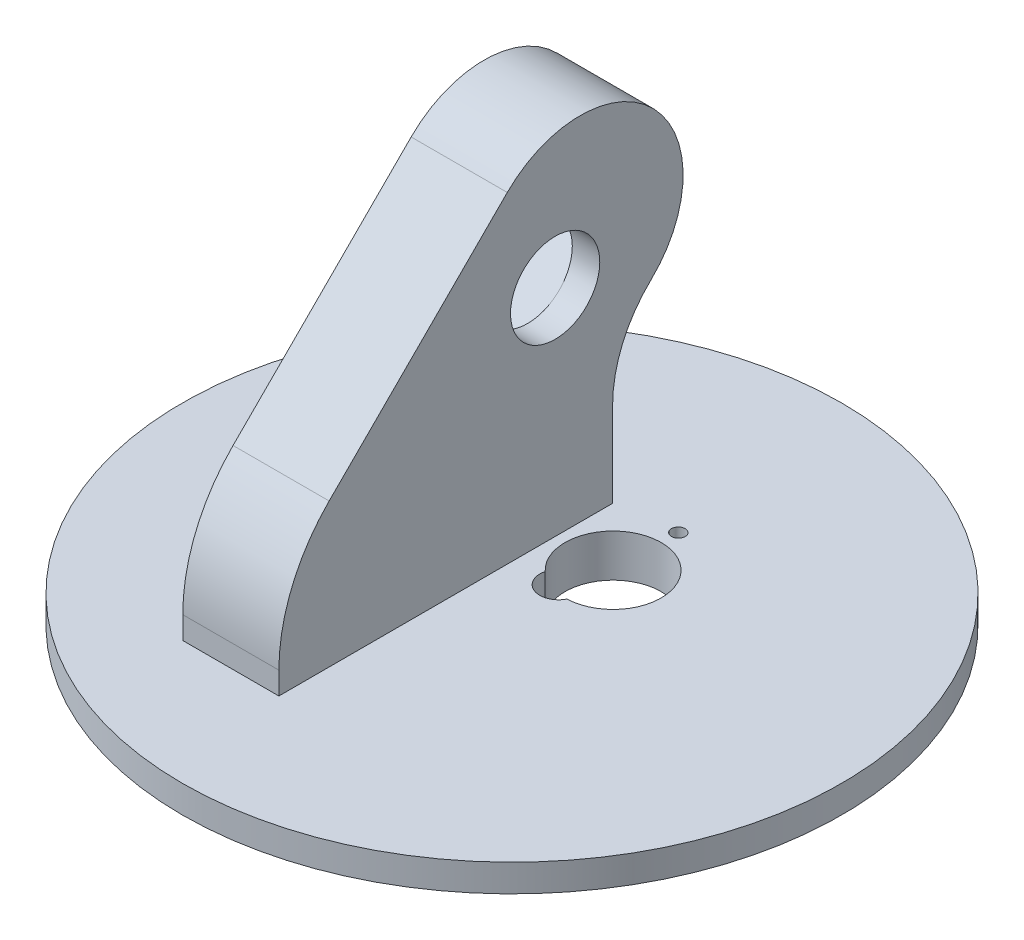
SolidWorks part; units mm, degrees
ref_plane "Front Plane" through (0, 0, 0) normal (0, 0, 1) x (1, 0, 0)
ref_plane "Top Plane" through (0, 0, 0) normal (0, 1, 0) x (1, 0, 0)
ref_plane "Right Plane" through (0, 0, 0) normal (1, 0, 0) x (0, 0, -1)
sketch "Sketch2" plane through (0, 0, 0) normal (0, 1, 0) x (1, 0, 0)
  circle A0 centre (0, 0) radius 48
  dimension "D1" = 96
extrude "Boss-Extrude1" add sketch "Sketch2" along normal blind 4
ref_plane "Plane1" through (-4, 0, 0) normal (1, 0, 0) x (0, 0, -1)
sketch "Sketch7" plane through (-4, 0, 0) normal (1, 0, 0) x (0, 0, -1)
  line L0 (18.6521, 16.3561) -> (18.6521, 4)
  line L5 (48, 4) -> (-48, 4) construction
  line L6 (-22.6311, 24.9401) -> (3.3119, 50.8831)
  line L7 (-43.5609, 4) -> (18.6521, 4)
  line L11 (-29.9535, 4) -> (-29.9535, 7.2624)
  arc A4 (24.252, 29.4036) -> (3.3119, 50.8831) centre (13.9185, 40.2765) ccw
  arc A5 (24.252, 29.4036) -> (18.6521, 16.3561) centre (36.6521, 16.3561) ccw
  arc A6 (-22.6311, 24.9401) -> (-29.9535, 7.2624) centre (-4.9535, 7.2624) ccw
  dimension "D1" = 25
  dimension "D4" = 30
  dimension "D3" = 18
  dimension "D5" = 45
extrude "Boss-Extrude2" add sketch "Sketch7" against normal blind 14 contours A5 A4 L6 L7 L0 | A4 | A4 | A4 | L6 A6 L7 region at (-4, 26.0967, -1.8639)
ref_plane "Plane2" through (-6, 0, 0) normal (1, 0, 0) x (0, 0, -1)
sketch "Sketch31" plane through (-18, 10.4618, -5.3595) normal (-1, 0, 0) x (0, 0, 1)
  line L0 (-5.4155, 34.0546) -> (11.7496, 18.7458)
  line L1 (11.7496, 18.7458) -> (3.0968, 9.0438)
  line L2 (3.0968, 9.0438) -> (-14.0683, 24.3526)
  line L3 (-14.0683, 24.3526) -> (-5.4155, 34.0546)
  circle A0 centre (-4.9225, 24.9054) radius 6.5
  dimension "D1" = 6.5
extrude "Cut-Extrude18" cut sketch "Sketch31" against normal through all contours A0
extrude "Cut-Extrude19" cut sketch "Sketch31<3>" against normal blind 10 contours L0 L1 L2 L3
sketch "Sketch31<3>" plane through (-18, 10.4618, -5.3595) normal (-1, 0, 0) x (0, 0, 1) same geometry as "Sketch31"
sketch "Sketch32" plane through (-18, 0, 0) normal (-1, 0, 0) x (0, 0, 1)
  line L0 (6.3901, 29.2076) -> (-2.2627, 19.5056) construction
  circle A0 centre (-17.0806, 41.2645) radius 1
  circle A1 centre (3.9294, 22.6926) radius 1
  arc A3 (-14.6084, 40.2182) -> (-15.5944, 39.1126) centre (-10.282, 35.3672) ccw construction
  dimension "D1" = 2.5
  dimension "D2" = 2.5
extrude "Cut-Extrude20" cut sketch "Sketch32" against normal blind 4.5
sketch "Sketch33" plane through (0, 0, 0) normal (0, -1, 0) x (1, 0, 0)
  circle A0 centre (0, 0) radius 43.5
extrude "Boss-Extrude3" add sketch "Sketch33" along normal blind 2.2
sketch "Sketch35" plane through (-3.1928, 4, -10.2509) normal (0, 1, 0) x (1, 0, 0)
  circle A0 centre (7.6655, 0) radius 7
extrude "Cut-Extrude22" cut sketch "Sketch35" against normal through all
sketch "Sketch36" plane through (0, 4, 0) normal (0, 1, 0) x (1, 0, 0)
  circle A0 centre (2.3101, 4.4441) radius 2.7018
extrude "Cut-Extrude24" cut sketch "Sketch36" against normal through all contours A0
sketch "Sketch37" plane through (0, 4, 0) normal (0, 1, 0) x (1, 0, 0)
  circle A0 centre (4.4727, 19.7509) radius 1
  arc A1 (4.7366, 3.2559) -> (-0.3026, 5.1326) centre (4.4727, 10.2509) ccw construction
  dimension "D1" = 2.5
extrude "Cut-Extrude25" cut sketch "Sketch37" against normal blind 4.5
